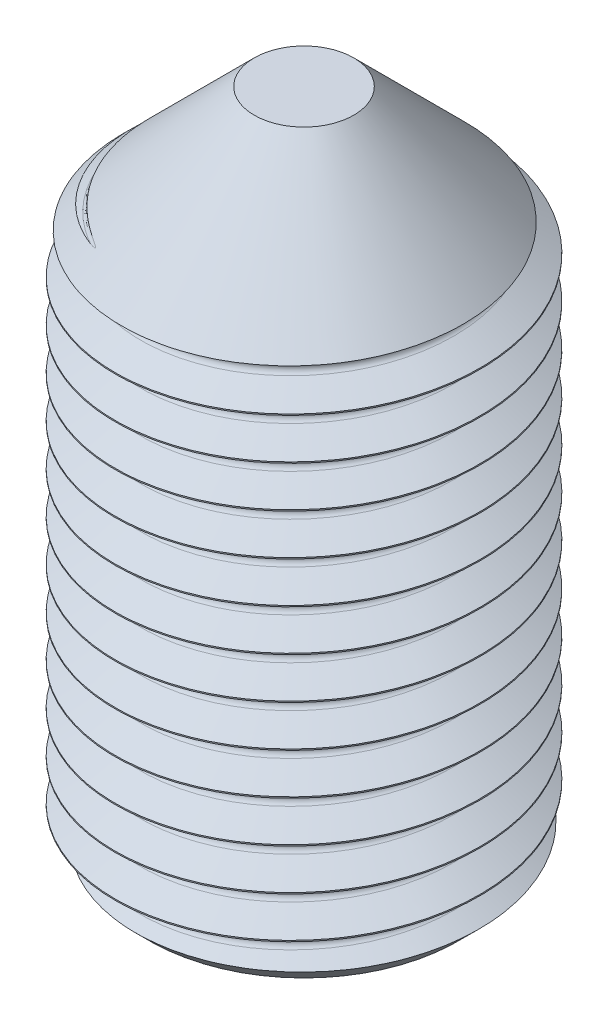
SolidWorks part; units mm, degrees
ref_plane "Front Plane" through (0, 0, 0) normal (0, 0, 1) x (1, 0, 0)
ref_plane "Top Plane" through (0, 0, 0) normal (0, 1, 0) x (1, 0, 0)
ref_plane "Right Plane" through (0, 0, 0) normal (1, 0, 0) x (0, 0, -1)
sketch "Sketch1" plane through (0, 0, 0) normal (0, 1, 0) x (1, 0, 0)
  circle A0 centre (0, 0) radius 11
  dimension "D1" = 22
extrude "Boss-Extrude1" add sketch "Sketch1" along normal mid plane 40
sketch "Sketch2" plane through (0, 0, 0) normal (0, 0, 1) x (1, 0, 0)
  line L0 (3, 20) -> (19.6582, 3.3418)
  line L1 (19.6582, 3.3418) -> (19.6582, -9.6418)
  line L2 (19.6582, -9.6418) -> (9.3, -20)
  line L3 (9.3, -20) -> (9.3, -23.2867)
  line L4 (9.3, -23.2867) -> (28.4292, -23.2867)
  line L5 (28.4292, -23.2867) -> (28.4292, 30.8739)
  line L6 (28.4292, 30.8739) -> (3, 30.8739)
  line L7 (3, 30.8739) -> (3, 20)
  line L8 (0, 0) -> (0, -3.1523) construction
  line L9 (11, 20) -> (-11, 20) construction
  line L10 (-11, -20) -> (11, -20) construction
  dimension "D1" = 6
  dimension "D2" = 18.6
  dimension "D3" = 135
  dimension "D4" = 135
revolve "Cut-Revolve1" cut sketch "Sketch2" angle 360 about L8
sketch "Sketch3" plane through (0, -20, 0) normal (0, -1, 0) x (1, 0, 0)
  line L1 (6.1, -3.5218) -> (6.1, 3.5218)
  line L2 (6.1, 3.5218) -> (0, 7.0437)
  line L3 (0, 7.0437) -> (-6.1, 3.5218)
  line L4 (-6.1, 3.5218) -> (-6.1, -3.5218)
  line L5 (-6.1, -3.5218) -> (0, -7.0437)
  line L6 (0, -7.0437) -> (6.1, -3.5218)
  circle A0 centre (0, 0) radius 6.1 construction
  dimension "D1" = 12.2
extrude "Cut-Extrude1" cut sketch "Sketch3" against normal blind 11
sketch "Sketch4" plane through (0, -20, 0) normal (0, -1, 0) x (1, 0, 0)
  circle A0 centre (0, 0) radius 11 construction
  circle A1 centre (0, 0) radius 11
curve "Helix/Spiral1" pitch 2.5 height 36.25 turns 14.5
sketch "Sketch5" plane through (0, 0, 0) normal (0, 0, 1) x (1, 0, 0)
  line L1 (11.0626, -19.0492) -> (9.4396, -19.9863)
  line L2 (9.4396, -20.6112) -> (11.0626, -21.5482)
  line L3 (11.0626, -21.5482) -> (11.0626, -19.0492)
  circle A0 centre (10.3412, -20.2987) radius 0.7214 construction
  arc A1 (9.4396, -19.9863) -> (9.4396, -20.6112) centre (9.6199, -20.2987) ccw
  dimension "D2" = 0.3608
  dimension "D1" = 2.499
sweep "Cut-Sweep1" cut profiles "Sketch5" path "Helix/Spiral1"
sketch "Sketch6" plane through (0, -20, 0) normal (0, -1, 0) x (1, 0, 0)
  circle A0 centre (0, 0) radius 7.0437
extrude "Cut-Extrude2" cut sketch "Sketch6" against normal blind 1.5 draft 75
